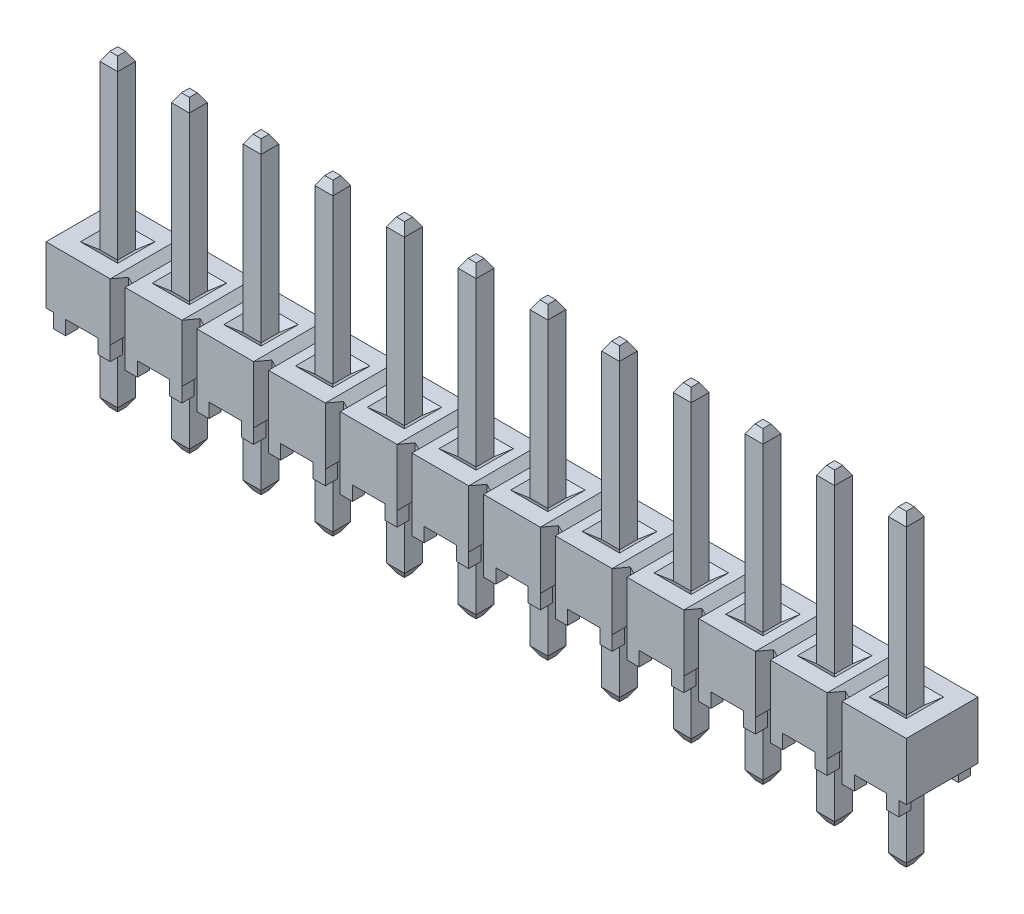
SolidWorks part; units mm, degrees
ref_plane "Front" through (0, 0, 0) normal (0, 0, 1) x (1, 0, 0)
ref_plane "Top" through (0, 0, 0) normal (0, 1, 0) x (1, 0, 0)
ref_plane "Right" through (0, 0, 0) normal (1, 0, 0) x (0, 0, -1)
sketch "Sketch3" plane through (0, 0, 0) normal (0, 0, 1) x (1, 0, 0)
  line L0 (0, 0.508) -> (0.2642, 0.508)
  line L1 (0, 2.54) -> (2.54, 2.54)
  line L2 (0, 2.54) -> (0, 0.508)
  line L3 (0.2642, 0) -> (0.696, 0)
  line L4 (2.54, 2.54) -> (2.54, 0.508)
  line L5 (0.2642, 0.508) -> (0.2642, 0)
  line L6 (0.696, 0.508) -> (0.696, 0)
  line L7 (0.696, 0.508) -> (1.844, 0.508)
  line L8 (1.844, 0.508) -> (1.844, 0)
  line L9 (1.844, 0) -> (2.2758, 0)
  line L10 (2.2758, 0) -> (2.2758, 0.508)
  line L11 (2.2758, 0.508) -> (2.54, 0.508)
  line L12 (1.27, 0.508) -> (1.27, 3.0515) construction
  dimension "D1" = 1.27
  dimension "D2" = 0.2642
  dimension "D3" = 0.4318
  dimension "D4" = 0.508
  dimension "D5" = 2.54
extrude "Main Body" add sketch "Sketch3" along normal mid plane 2.54
ref_plane "Plane3" through (1.27, 0, 0) normal (1, 0, 0) x (0, 0, -1)
sketch "Sketch4" plane through (2.54, 2.54, 0) normal (-1, 0, 0) x (0, -1, 0)
  line L1 (0, 0) -> (1.693, 0) construction
  line L2 (0, 1.27) -> (0, -1.27) construction
  line L3 (2.54, 1.27) -> (2.54, -1.27) construction
  line L4 (2.54, 0.8382) -> (2.032, 0.8382)
  line L7 (2.54, 0.8382) -> (2.54, -0.8382)
  line L8 (2.54, -0.8382) -> (2.032, -0.8382)
  line L9 (2.032, 0.8382) -> (2.032, -0.8382)
  line L10 (2.032, 1.27) -> (2.032, -1.27) construction
  line L25 (2.032, 1.27) -> (2.54, 1.27) construction
  dimension "D1" = 0.4318
extrude "Base Cut" cut sketch "Sketch4" along normal blind 2.54
pattern_linear "Main Body Pattern" count 12 spacing 2.54 along (-1, 0, 0) of "Main Body", "Base Cut"
sketch "Sketch19" plane through (0, 2.54, 0) normal (0, 1, 0) x (-1, 0, 0)
  line L0 (-1.5748, 0) -> (-0.9652, 0) construction
  line L1 (-1.5748, 0.3048) -> (-0.9652, 0.3048)
  line L2 (-1.5748, 0.3048) -> (-1.5748, -0.3048)
  line L3 (-1.5748, -0.3048) -> (-0.9652, -0.3048)
  line L4 (-0.9652, 0.3048) -> (-0.9652, -0.3048)
  line L6 (-2.54, 1.27) -> (-2.54, -1.27) construction
  line L8 (-2.54, 1.27) -> (27.94, 1.27) construction
  dimension "D1" = 0.6096
  dimension "D2" = 0.9652
  dimension "D3" = 1.27
extrude "Pin Cut" cut sketch "Sketch19" against normal through all
chamfer "Pin Chamfer" distance 0.3556 distance2 0.254 8 edges at (1.27, 0.508, -0.3048) (0.9652, 0.508, 0) (1.27, 0.508, 0.3048) (1.5748, 0.508, 0) (1.5748, 2.54, 0) (1.27, 2.54, -0.3048) (0.9652, 2.54, 0) (1.27, 2.54, 0.3048)
pattern_linear "Pin Pattern" count 12 spacing 2.54 along (-1, 0, 0) of "Pin Cut", "Pin Chamfer"
sketch "Sketch5" plane through (0, 0, 0) normal (0, 1, 0) x (1, 0, 0)
  line L0 (0, 0) -> (0, 2.9019) construction
  line L1 (-0.2642, 1.27) -> (0.2642, 1.27)
  line L2 (2.54, -1.27) -> (-27.94, -1.27) construction
  line L3 (0.2642, 1.27) -> (0.127, 0.762)
  line L4 (0.127, 0.762) -> (-0.127, 0.762)
  line L5 (-0.127, 0.762) -> (-0.2642, 1.27)
  line L10 (-0.127, -0.762) -> (-0.2642, -1.27)
  line L11 (0.127, -0.762) -> (-0.127, -0.762)
  line L12 (0.2642, -1.27) -> (0.127, -0.762)
  line L13 (-0.2642, -1.27) -> (0.2642, -1.27)
  dimension "D1" = 0.508
  dimension "D2" = 0.254
  dimension "D3" = 0.254
  dimension "D4" = 0.5283
  dimension "R" = 2.54
  dimension "D5" = 0.508
  dimension "D6" = 0.5283
extrude "Slot Cut-1" cut sketch "Sketch5" along normal through all
sketch "Sketch7" plane through (0, 0, 1.27) normal (0, 0, 1) x (1, 0, 0)
  line L0 (-0.2642, 2.54) -> (0, 2.2758)
  line L1 (0, 2.2758) -> (0.2642, 2.54)
  line L2 (0.2642, 2.54) -> (-0.2642, 2.54)
  line L3 (0, 2.54) -> (0, 1.8658) construction
  line L4 (2.54, 1.524) -> (1.3831, 1.524) construction
  line L5 (2.54, 0.508) -> (2.54, 2.54) construction
  line L6 (0.2642, 0.508) -> (-0.2642, 0.508)
  line L7 (0, 0.7722) -> (0.2642, 0.508)
  line L8 (-0.2642, 0.508) -> (0, 0.7722)
  line L18 (2.54, 0.508) -> (2.54, 2.54) construction
  line L19 (2.54, 2.54) -> (0.2642, 2.54) construction
  dimension "D1" = 0.2642
  dimension "D4" = 2.54
  dimension "D5" = 0.5283
extrude "Slot Cut-2" cut sketch "Sketch7" against normal blind 2.54
pattern_linear "Slot Pattern" count 11 spacing 2.54 along (-1, 0, 0) of "Slot Cut-1", "Slot Cut-2"
sketch "Sketch9" plane through (1.27, 0, 0) normal (1, 0, 0) x (0, 0, -1)
  line L0 (0, -2.54) -> (0, -0.993) construction
  line L1 (-0.3175, 8.382) -> (0.3175, 8.382)
  line L2 (-0.3175, 8.382) -> (-0.3175, -2.54)
  line L3 (-0.3175, -2.54) -> (0.3175, -2.54)
  line L4 (0.3175, 8.382) -> (0.3175, -2.54)
  line L5 (-1.27, 0) -> (-0.8382, 0) construction
  line L7 (-1.27, 0.508) -> (-1.27, 2.54) construction
  line L8 (-1.27, 2.54) -> (1.27, 2.54) construction
  dimension "D1" = 0.635
  dimension "D2" = 1.27
  dimension "SC" = 5.842
  dimension "SA" = 2.54
extrude "Straight Lead " add sketch "Sketch9" along normal mid plane 0.635
chamfer "Lead Chamfer" distance 0.1753 distance2 0.3048 8 edges at (1.5875, -2.54, 0) (1.27, -2.54, -0.3175) (1.27, 8.382, 0.3175) (0.9525, -2.54, 0) (1.27, -2.54, 0.3175) (0.9525, 8.382, 0) (1.27, 8.382, -0.3175) (1.5875, 8.382, 0)
pattern_linear "Straight L Pattern" count 12 spacing 2.54 along (-1, 0, 0) of "Straight Lead ", "Lead Chamfer"
sketch "Sketch24" plane through (0, 2.54, 0) normal (0, 1, 0) x (-1, 0, 0)
  line L0 (-1.5875, 1.778) -> (-0.9525, 1.778)
  line L1 (-0.9525, 1.778) -> (-0.2642, 1.27)
  line L2 (-2.54, 1.27) -> (-0.2642, 1.27) construction
  line L3 (-2.2758, 1.27) -> (-1.5875, 1.778)
  line L4 (-1.27, 1.778) -> (-1.27, -0.1201) construction
  line L7 (-0.2642, 1.27) -> (-2.2758, 1.27)
  dimension "D1" = 0.635
  dimension "D2" = 0.508
sketch "Sketch20" plane through (1.27, 0, 0) normal (1, 0, 0) x (0, 0, -1)
  line L0 (0, 3.1438) -> (0, -1.524) construction
  line L1 (0, -1.524) -> (-4.0844, -1.524) construction
  line L2 (-1.27, 0) -> (-0.8382, 0) construction
  line L3 (-1.27, 0) -> (-1.27, 0.508) construction
  line L5 (-2.54, -1.8415) -> (-0.4445, -1.8415)
  line L6 (0.3175, 3.81) -> (0.3175, -1.0795)
  line L7 (-2.54, -1.2065) -> (-0.5715, -1.2065)
  line L8 (-0.3175, 3.81) -> (-0.3175, -0.9525)
  line L9 (-0.3175, 3.81) -> (0.3175, 3.81)
  line L10 (-2.54, -1.2065) -> (-2.54, -1.8415)
  line L11 (-1.27, 0.508) -> (-1.27, 2.54) construction
  line L12 (-1.27, 2.54) -> (1.27, 2.54) construction
  arc A0 (-0.4445, -1.8415) -> (0.3175, -1.0795) centre (-0.4445, -1.0795) ccw
  arc A1 (-0.5715, -1.2065) -> (-0.3175, -0.9525) centre (-0.5715, -0.9525) ccw
  dimension "D3" = 0.762
  dimension "D5" = 0.254
  dimension "D1" = 1.524
  dimension "D2" = 1.27
  dimension "D4" = 0.635
  dimension "A" = 1.27
  dimension "C" = 1.27
sketch "Sketch22" plane through (1.27, 0.5208, -3.4332) normal (1, 0, 0) x (0, 0, -1)
  line L0 (-0.8932, 3.1438) -> (-0.8932, -4.5848) construction
  line L1 (-0.8932, -4.5848) -> (-5.9732, -4.5848) construction
  line L2 (-4.7032, 2.0192) -> (-2.1632, 2.0192) construction
  line L5 (-5.9732, -4.9023) -> (-1.3377, -4.9023)
  line L6 (-0.5757, 3.2892) -> (-0.5757, -4.1403)
  line L7 (-5.9732, -4.2673) -> (-1.4647, -4.2673)
  line L8 (-1.2107, 3.2892) -> (-1.2107, -4.0133)
  line L9 (-1.2107, 3.2892) -> (-0.5757, 3.2892)
  line L10 (-5.9732, -4.2673) -> (-5.9732, -4.9023)
  line L13 (-4.7032, -0.0128) -> (-4.7032, 2.0192) construction
  line L15 (-4.7032, -0.5208) -> (-4.2714, -0.5208) construction
  arc A0 (-1.3377, -4.9023) -> (-0.5757, -4.1403) centre (-1.3377, -4.1403) ccw
  arc A1 (-1.4647, -4.2673) -> (-1.2107, -4.0133) centre (-1.4647, -4.0133) ccw
  dimension "D3" = 0.762
  dimension "D5" = 0.254
  dimension "D1" = 4.064
  dimension "D2" = 3.81
  dimension "D4" = 0.635
sketch "Sketch23" plane through (1.27, 1.2977, -6.8432) normal (1, 0, 0) x (0, 0, -1)
  line L0 (-1.7632, 3.1438) -> (-1.7632, -7.9017) construction
  line L1 (-1.7632, -7.9017) -> (-9.3832, -7.9017) construction
  line L2 (-8.1132, -0.7897) -> (-8.1132, 1.2423) construction
  line L3 (-8.1132, -1.2977) -> (-7.6814, -1.2977) construction
  line L5 (-9.3832, -8.2192) -> (-2.2077, -8.2192)
  line L6 (-1.4457, 2.5123) -> (-1.4457, -7.4572)
  line L7 (-9.3832, -7.5842) -> (-2.3347, -7.5842)
  line L8 (-2.0807, 2.5123) -> (-2.0807, -7.3302)
  line L9 (-2.0807, 2.5123) -> (-1.4457, 2.5123)
  line L10 (-9.3832, -7.5842) -> (-9.3832, -8.2192)
  line L13 (-8.1132, 1.2423) -> (-5.5732, 1.2423) construction
  arc A0 (-2.2077, -8.2192) -> (-1.4457, -7.4572) centre (-2.2077, -7.4572) ccw
  arc A1 (-2.3347, -7.5842) -> (-2.0807, -7.3302) centre (-2.3347, -7.3302) ccw
  dimension "D3" = 0.762
  dimension "D5" = 0.254
  dimension "D1" = 6.35
  dimension "D2" = 6.604
  dimension "D4" = 0.635
ref_plane "Crimp Plane" through (-11.43, 0, 0) normal (1, 0, 0) x (0, 0, -1)
ref_plane "Crimp Plane-S" through (-13.97, 0, 0) normal (1, 0, 0) x (0, 0, -1)
sketch "Sketch15" plane through (-11.43, 0, 0) normal (1, 0, 0) x (0, 0, -1)
  line L0 (-0.8555, -1.016) -> (-2.0169, -1.016) construction
  line L2 (-0.3175, -0.762) -> (-0.3175, -1.27)
  line L3 (-1.27, 0) -> (-1.27, 0.508) construction
  line L4 (-0.3175, -1.27) -> (-0.1143, -1.016)
  line L5 (-0.1143, -1.016) -> (-0.3175, -0.762)
  line L6 (-0.3175, -3.0287) -> (-0.3175, -4.8055) construction
  line L8 (-1.27, 0) -> (-0.8382, 0) construction
  dimension "D1" = 0.9525
  dimension "D2" = 0.2032
  dimension "D3" = 0.508
  dimension "D4" = 1.016
sketch "Sketch16" plane through (-11.43, 0, 0) normal (1, 0, 0) x (0, 0, -1)
  line L0 (0.6945, -1.016) -> (2.3576, -1.016) construction
  line L1 (0.3175, -0.7747) -> (0.5207, -0.9398)
  line L3 (0.5207, -0.9398) -> (0.5207, -1.0922)
  line L4 (0.5207, -1.0922) -> (0.3175, -1.2573)
  line L5 (0.3175, -1.2573) -> (0.3175, -0.7747)
  line L8 (0.3175, -2.4554) -> (0.3175, -4.0395) construction
  line L11 (-1.27, 0.508) -> (-1.27, 2.54) construction
  line L12 (-1.27, 0) -> (-0.8382, 0) construction
  dimension "D1" = 1.5875
  dimension "D2" = 0.1524
  dimension "D3" = 0.2032
  dimension "D4" = 0.4826
  dimension "D5" = 1.016
sketch "Sketch17" plane through (-13.97, 0, 0) normal (1, 0, 0) x (0, 0, -1)
  line L0 (-0.2248, -1.016) -> (1.2324, -1.016) construction
  line L1 (0.3175, -1.6114) -> (0.3175, -2.5674) construction
  line L2 (0.3175, -0.762) -> (0.3175, -1.27)
  line L3 (0.3175, -0.762) -> (0.1143, -1.016)
  line L4 (0.1143, -1.016) -> (0.3175, -1.27)
  line L8 (-1.27, 0) -> (-1.27, 0.508) construction
  line L9 (-1.27, 0) -> (-0.8382, 0) construction
  dimension "D1" = 0.254
  dimension "D2" = 0.2032
  dimension "D3" = 1.5875
  dimension "D4" = 1.016
sketch "Sketch18" plane through (-13.97, 0, 0) normal (1, 0, 0) x (0, 0, -1)
  line L0 (-0.3175, -0.6988) -> (-0.3175, -1.8479) construction
  line L1 (-1.5126, -1.016) -> (-0.67, -1.016) construction
  line L2 (-0.3175, -0.7747) -> (-0.5207, -0.9398)
  line L3 (-0.5207, -0.9398) -> (-0.5207, -1.0922)
  line L4 (-0.5207, -1.0922) -> (-0.3175, -1.2573)
  line L5 (-0.3175, -1.2573) -> (-0.3175, -0.7747)
  line L7 (-1.27, 0) -> (-1.27, 0.508) construction
  line L8 (-1.27, 0) -> (-0.8382, 0) construction
  dimension "D1" = 0.2032
  dimension "D2" = 0.1524
  dimension "D3" = 0.9525
  dimension "D4" = 1.016
  dimension "D5" = 0.4826
ref_plane "S-Straight Polarize" through (2.54, 0, 0) normal (1, 0, 0) x (0, 0, -1)
ref_plane "D-Straight Polarize" through (-2.54, 0, 0) normal (1, 0, 0) x (0, 0, -1)
sketch "SS-Polarize Sketch" plane through (2.54, 0, 0) normal (1, 0, 0) x (0, 0, -1)
  line L0 (0, 40.64) -> (0, -22.86) construction
  line L1 (-0.381, 40.64) -> (0.381, 40.64)
  line L2 (-0.381, 40.64) -> (-0.381, 0.5055)
  line L3 (-1.27, 0.508) -> (1.27, 0.508) construction
  line L4 (0.381, 40.64) -> (0.381, 0.5055)
  line L5 (-1.27, 0.508) -> (-1.27, 2.54) construction
  line L6 (-0.635, 0.5055) -> (-0.635, -22.86)
  line L7 (0.635, 0.5055) -> (0.635, -22.86)
  line L8 (-0.635, 0.5055) -> (-0.381, 0.5055)
  line L9 (-0.635, -22.86) -> (0.635, -22.86)
  line L10 (0.381, 0.5055) -> (0.635, 0.5055)
  line L12 (-1.27, 2.54) -> (1.27, 2.54) construction
  dimension "D1" = 1.27
  dimension "D2" = 0.762
  dimension "D3" = 1.27
  dimension "D4" = 0.0025
  dimension "D5" = 38.1
  dimension "D6" = 63.5
sketch "Sketch31" plane through (0, 0, 0) normal (0, 0, 1) x (1, 0, 0)
  line L0 (-2.159, 0.508) -> (3.0527, 0.508)
  line L1 (3.683, 1.2204) -> (2.3826, 11.811)
  line L2 (2.3826, 11.811) -> (1.1031, 11.811)
  line L3 (1.1031, 11.811) -> (1.1031, 12.065)
  line L4 (1.1031, 12.065) -> (2.8987, 13.8606)
  line L5 (2.8987, 13.8606) -> (4.5017, 0.8053)
  line L6 (3.1151, -0.762) -> (-2.159, -0.762)
  line L7 (-2.159, -0.762) -> (-2.159, 0.508)
  line L8 (3.683, 1.2204) -> (3.683, -1.599) construction
  line L9 (2.54, 0.508) -> (2.54, 2.54) construction
  arc A0 (3.0527, 0.508) -> (3.683, 1.2204) centre (3.0527, 1.143) ccw
  arc A1 (4.5017, 0.8053) -> (3.1151, -0.762) centre (3.1151, 0.635) cw
  dimension "D1" = 0.635
  dimension "D7" = 1.397
  dimension "D2" = 45
  dimension "D3" = 0.254
  dimension "D4" = 0.762
  dimension "D5" = 1.27
  dimension "D6" = 83
  dimension "D8" = 11.303
  dimension "D9" = 1.27
  dimension "D10" = 5.842
  dimension "D11" = 1.143
ref_plane "Mid Plane" through (-12.7, 0, 0) normal (1, 0, 0) x (0, 0, -1)
